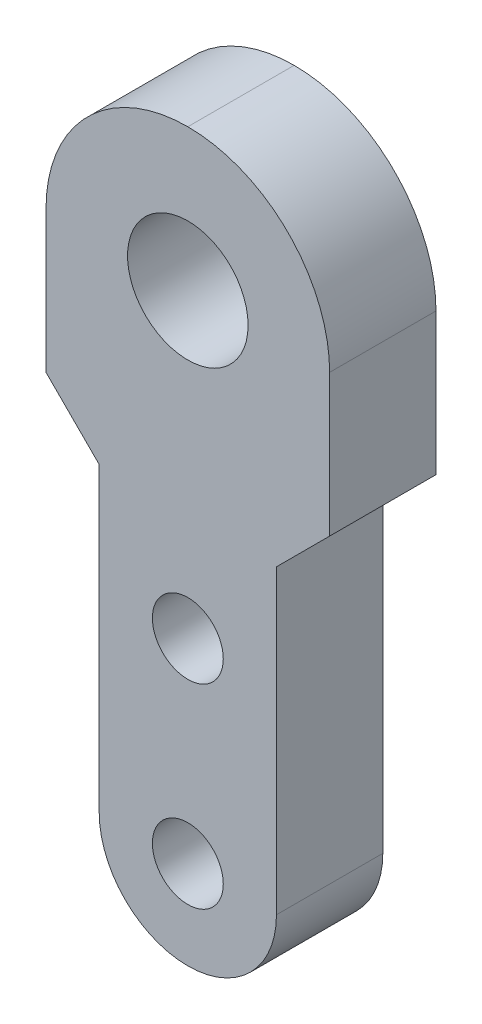
SolidWorks part; units mm, degrees
ref_plane "Front" through (0, 0, 0) normal (0, 0, 1) x (1, 0, 0)
ref_plane "Top" through (0, 0, 0) normal (0, 1, 0) x (1, 0, 0)
ref_plane "Right" through (0, 0, 0) normal (1, 0, 0) x (0, 0, -1)
sketch "Esquisse1" plane through (0, 0, 0) normal (0, 0, 1) x (1, 0, 0)
  line L1 (0, 0) -> (10, 0)
  line L2 (0, 0) -> (0, 25)
  line L3 (0, 25) -> (10, 25)
  line L4 (10, 0) -> (10, 25)
  dimension "D1" = 10
  dimension "D2" = 25
extrude "Boss.-Extru.1" add sketch "Esquisse1" along normal blind 6
sketch "Esquisse2" plane through (0, 0, 6) normal (0, 0, 1) x (1, 0, 0)
  line L0 (5, 25) -> (5, 41) construction
  line L1 (10, 25) -> (0, 25) construction
  line L2 (13, 41) -> (-3, 41)
  line L3 (-3, 41) -> (-3, 25)
  line L4 (-3, 25) -> (13, 25)
  line L5 (13, 41) -> (13, 25)
  dimension "D1" = 16
  dimension "D2" = 16
extrude "Boss.-Extru.2" add sketch "Esquisse2" against normal up to vertex (6 mm away) up to point (10, 0, 0)
sketch "Esquisse3" plane through (0, 0, 6) normal (0, 0, 1) x (1, 0, 0)
  line L0 (5, 41) -> (5, 25) construction
  line L1 (13, 41) -> (-3, 41) construction
  line L2 (5, 25) -> (0, 25) construction
  line L3 (5, 0) -> (5, 16) construction
  line L4 (0, 0) -> (10, 0) construction
  circle A0 centre (5, 33) radius 3.4
  circle A1 centre (5, 16) radius 2
  circle A2 centre (5, 5) radius 2
  dimension "D1" = 6.8
  dimension "D2" = 4
  dimension "D3" = 11
  dimension "D4" = 5
extrude "Enlèv. mat.-Extru.1" cut sketch "Esquisse3" against normal through all
fillet "Congé1" radius 8 2 edges at (13, 41, 3) (-3, 41, 3)
chamfer "Chanfrein1" distance 3 angle 45 2 edges at (10, 25, 3) (0, 25, 3)
fillet "Congé2" radius 5 2 edges at (10, 0, 3) (0, 0, 3)
